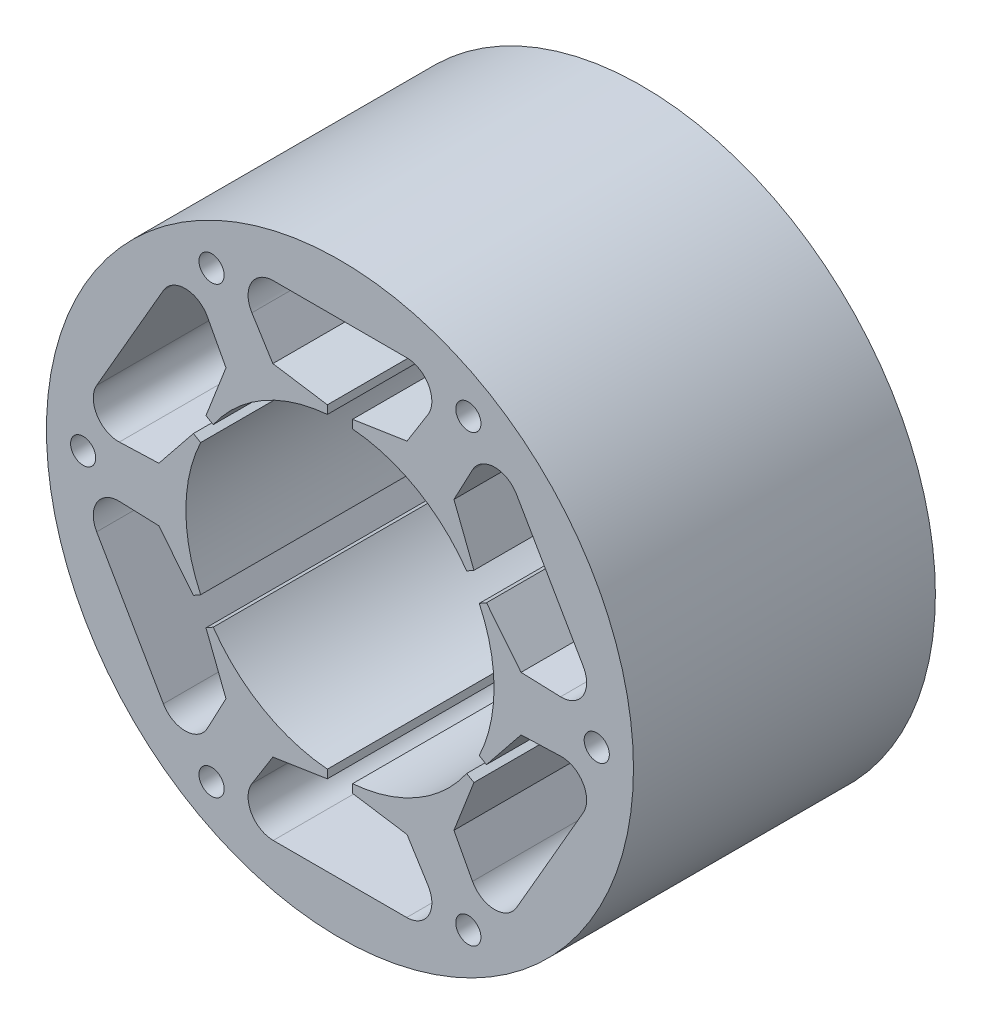
SolidWorks part; units mm, degrees
ref_plane "Ön Düzlem" through (0, 0, 0) normal (0, 0, 1) x (1, 0, 0)
ref_plane "Üst Düzlem" through (0, 0, 0) normal (0, 1, 0) x (1, 0, 0)
ref_plane "Sağ Düzlem" through (0, 0, 0) normal (1, 0, 0) x (0, 0, -1)
sketch "Çizim2" plane through (0, 0, 0) normal (0, 0, 1) x (1, 0, 0)
  line L0 (-15.1101, 10.4559) -> (-15.9761, 10.9559)
  line L1 (-1.5, 19.3137) -> (-1.5, 18.3137)
  line L2 (-8, 20.3137) -> (-1.5, 19.3137)
  line L3 (-10.5, 24.3137) -> (-8, 20.3137)
  line L4 (7.956, 28.9037) -> (-7.956, 28.9037)
  line L5 (8, 20.3137) -> (10.5, 24.3137)
  line L6 (1.5, 19.3137) -> (8, 20.3137)
  line L7 (1.5, 18.3137) -> (1.5, 19.3137)
  line L8 (15.9761, 10.9559) -> (15.1101, 10.4559)
  line L9 (13.5922, 17.085) -> (15.9761, 10.9559)
  line L10 (15.8063, 21.2501) -> (13.5922, 17.085)
  line L11 (29.0093, 7.5617) -> (21.0533, 21.3419)
  line L12 (21.5922, 3.2286) -> (26.3063, 3.0636)
  line L13 (17.4761, 8.3578) -> (21.5922, 3.2286)
  line L14 (16.6101, 7.8578) -> (17.4761, 8.3578)
  line L15 (17.4761, -8.3578) -> (16.6101, -7.8578)
  line L16 (21.5922, -3.2286) -> (17.4761, -8.3578)
  line L17 (26.3063, -3.0636) -> (21.5922, -3.2286)
  line L18 (21.0533, -21.3419) -> (29.0093, -7.5617)
  line L19 (13.5922, -17.085) -> (15.8063, -21.2501)
  line L20 (15.9761, -10.9559) -> (13.5922, -17.085)
  line L21 (15.1101, -10.4559) -> (15.9761, -10.9559)
  line L22 (1.5, -19.3137) -> (1.5, -18.3137)
  line L23 (8, -20.3137) -> (1.5, -19.3137)
  line L24 (10.5, -24.3137) -> (8, -20.3137)
  line L25 (-7.956, -28.9037) -> (7.956, -28.9037)
  line L26 (-8, -20.3137) -> (-10.5, -24.3137)
  line L27 (-1.5, -19.3137) -> (-8, -20.3137)
  line L28 (-1.5, -18.3137) -> (-1.5, -19.3137)
  line L29 (-15.9761, -10.9559) -> (-15.1101, -10.4559)
  line L30 (-13.5922, -17.085) -> (-15.9761, -10.9559)
  line L31 (-15.8063, -21.2501) -> (-13.5922, -17.085)
  line L32 (-29.0093, -7.5617) -> (-21.0533, -21.3419)
  line L33 (-21.5922, -3.2286) -> (-26.3063, -3.0636)
  line L34 (-17.4761, -8.3578) -> (-21.5922, -3.2286)
  line L35 (-16.6101, -7.8578) -> (-17.4761, -8.3578)
  line L36 (-17.4761, 8.3578) -> (-16.6101, 7.8578)
  line L37 (-21.5922, 3.2286) -> (-17.4761, 8.3578)
  line L38 (-26.3063, 3.0636) -> (-21.5922, 3.2286)
  line L39 (-21.0533, 21.3419) -> (-29.0093, 7.5617)
  line L40 (-13.5922, 17.085) -> (-15.8063, 21.2501)
  line L41 (-15.9761, 10.9559) -> (-13.5922, 17.085)
  circle A0 centre (-15.3101, -26.5179) radius 1.5
  circle A1 centre (30.6203, 0) radius 1.5
  circle A2 centre (-15.3101, 26.5179) radius 1.5
  circle A3 centre (0, 0) radius 35
  arc A4 (-1.5, 18.3137) -> (-15.1101, 10.4559) centre (0, 0) ccw
  arc A5 (-7.956, 28.9037) -> (-10.5, 24.3137) centre (-7.956, 25.9037) ccw
  arc A6 (10.5, 24.3137) -> (7.956, 28.9037) centre (7.956, 25.9037) ccw
  arc A7 (15.1101, 10.4559) -> (1.5, 18.3137) centre (0, 0) ccw
  arc A8 (21.0533, 21.3419) -> (15.8063, 21.2501) centre (18.4552, 19.8419) ccw
  arc A9 (26.3063, 3.0636) -> (29.0093, 7.5617) centre (26.4112, 6.0617) ccw
  arc A10 (16.6101, -7.8578) -> (16.6101, 7.8578) centre (0, 0) ccw
  arc A11 (29.0093, -7.5617) -> (26.3063, -3.0636) centre (26.4112, -6.0617) ccw
  arc A12 (15.8063, -21.2501) -> (21.0533, -21.3419) centre (18.4552, -19.8419) ccw
  arc A13 (1.5, -18.3137) -> (15.1101, -10.4559) centre (0, 0) ccw
  arc A14 (7.956, -28.9037) -> (10.5, -24.3137) centre (7.956, -25.9037) ccw
  arc A15 (-10.5, -24.3137) -> (-7.956, -28.9037) centre (-7.956, -25.9037) ccw
  arc A16 (-15.1101, -10.4559) -> (-1.5, -18.3137) centre (0, 0) ccw
  arc A17 (-21.0533, -21.3419) -> (-15.8063, -21.2501) centre (-18.4552, -19.8419) ccw
  arc A18 (-26.3063, -3.0636) -> (-29.0093, -7.5617) centre (-26.4112, -6.0617) ccw
  arc A19 (-16.6101, 7.8578) -> (-16.6101, -7.8578) centre (0, 0) ccw
  arc A20 (-29.0093, 7.5617) -> (-26.3063, 3.0636) centre (-26.4112, 6.0617) ccw
  arc A21 (-15.8063, 21.2501) -> (-21.0533, 21.3419) centre (-18.4552, 19.8419) ccw
  circle A22 centre (15.3101, 26.5179) radius 1.5
  circle A23 centre (15.3101, -26.5179) radius 1.5
  circle A24 centre (-30.6203, 0) radius 1.5
extrude "Yükseklik-Ekstrüzyon1" add sketch "Çizim2" along normal blind 36
